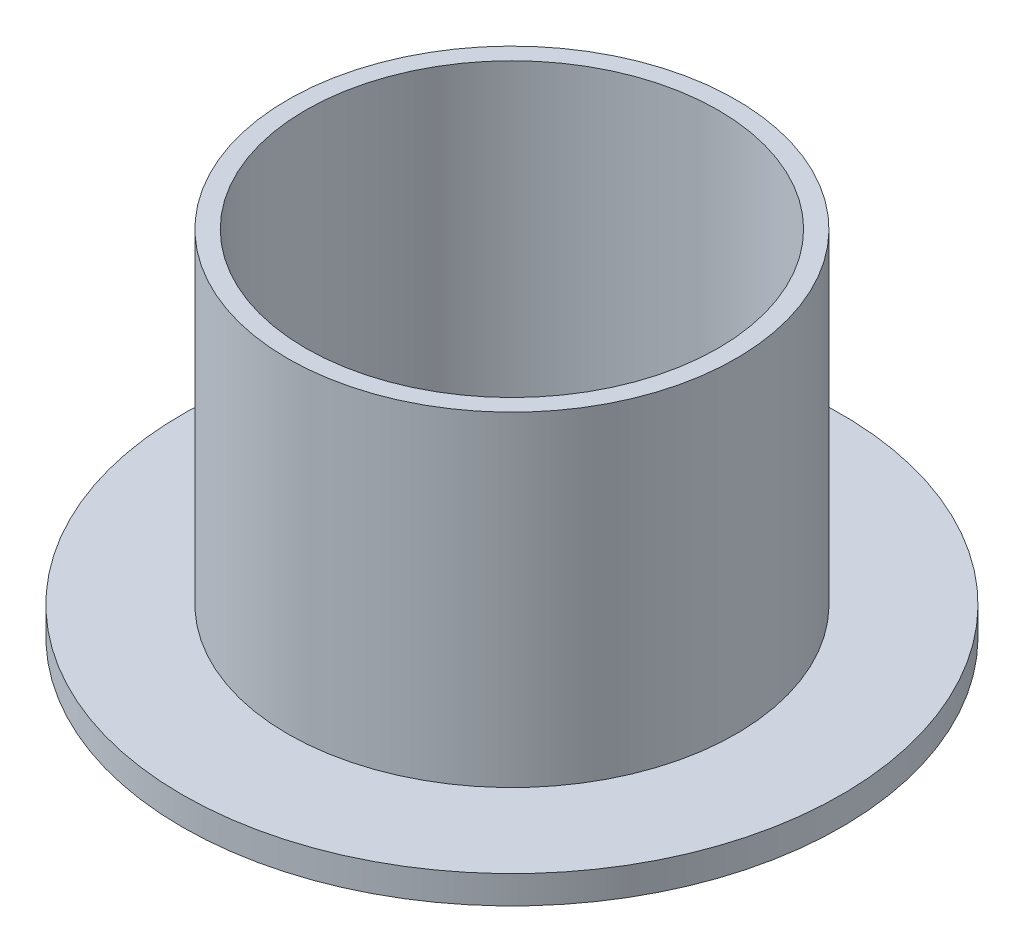
SolidWorks part; units mm, degrees
material "AISI 304"
ref_plane "Front Plane" through (0, 0, 0) normal (0, 0, 1) x (1, 0, 0)
ref_plane "Top Plane" through (0, 0, 0) normal (0, 1, 0) x (1, 0, 0)
ref_plane "Right Plane" through (0, 0, 0) normal (1, 0, 0) x (0, 0, -1)
sketch "Sketch1" plane through (0, 0, 0) normal (0, 1, 0) x (1, 0, 0)
  circle A0 centre (0, 0) radius 23.368
  circle A1 centre (0, 0) radius 25.4
  circle A2 centre (0, 0) radius 37.338
  dimension "D1" = 46.736
  dimension "D2" = 50.8
  dimension "D3" = 74.676
extrude "Boss-Extrude1" add sketch "Sketch1" along normal blind 40.005 contours A1 A0 region at (-24.6816, 0, 0)
extrude "Boss-Extrude2" add sketch "Sketch1<3>" along normal blind 3.175 contours A2 A1 region at (-36.2819, 0, 0)
sketch "Sketch1<3>" plane through (0, 0, 0) normal (0, 1, 0) x (1, 0, 0) same geometry as "Sketch1"
